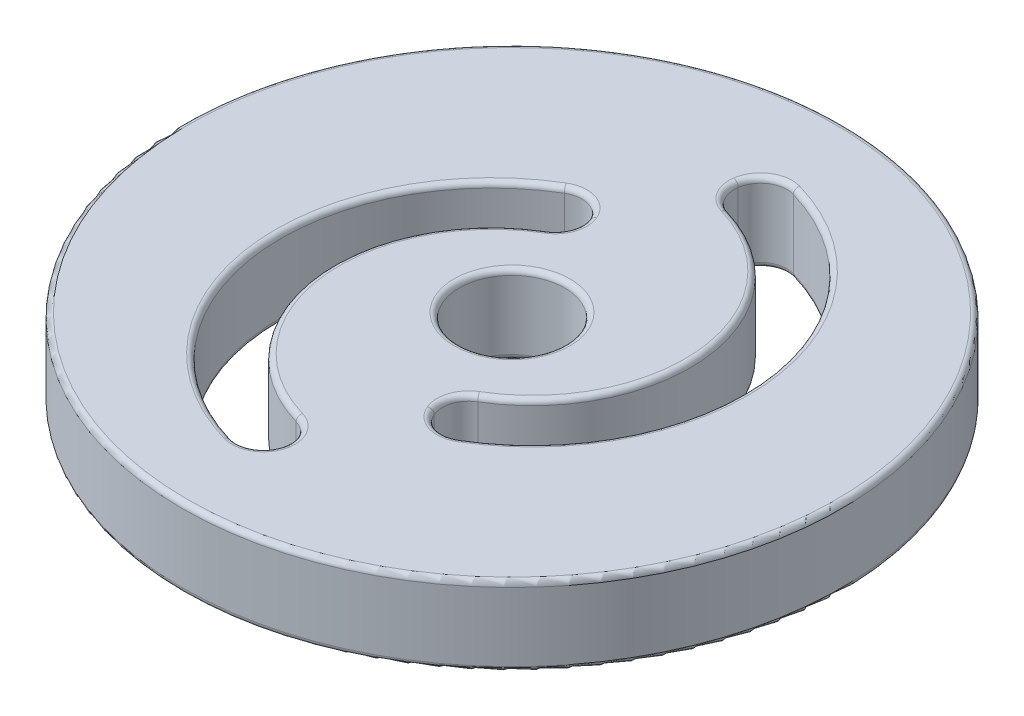
SolidWorks part; units mm, degrees
ref_plane "前视基准面" through (0, 0, 0) normal (0, 0, 1) x (1, 0, 0)
ref_plane "上视基准面" through (0, 0, 0) normal (0, 1, 0) x (1, 0, 0)
ref_plane "右视基准面" through (0, 0, 0) normal (1, 0, 0) x (0, 0, -1)
other "Configuration Table"
sketch "草图1" plane through (0, 0, 0) normal (0, 1, 0) x (1, 0, 0)
  circle A0 centre (0, 0) radius 125
  circle A1 centre (0, 0) radius 20
  dimension "D1" = 40
  dimension "D2" = 250
extrude "凸台-拉伸1" add sketch "草图1" along normal blind 30
sketch "草图2" plane through (0, 30, 0) normal (0, 1, 0) x (1, 0, 0)
  line L0 (0, 0) -> (0, 150) construction
  line L1 (0, 0) -> (-60.6659, 166.6783) construction
  line L2 (1.3957, 96.5021) -> (-1.3957, 76.6979)
  line L3 (13.256, -37.7534) -> (20.9461, -56.2159)
  line L6 (-13.256, 37.7534) -> (-20.9461, 56.2159)
  line L7 (-1.3957, -96.5021) -> (1.3957, -76.6979)
  arc A0 (0, 86.6) -> (17.101, -46.9846) centre (-9.7443, 17.4657) cw construction
  arc A1 (-1.3957, 76.6979) -> (13.256, -37.7534) centre (-9.7443, 17.4657) cw
  arc A2 (1.3957, 96.5021) -> (20.9461, -56.2159) centre (-9.7443, 17.4657) cw
  arc A3 (-1.3957, 76.6979) -> (13.256, -37.7534) centre (-9.7443, 17.4657) cw construction
  circle A4 centre (0, 0) radius 20 construction
  arc A5 (0, 86.6) -> (17.101, -46.9846) centre (-9.7443, 17.4657) cw construction
  arc A8 (-1.3957, -96.5021) -> (-20.9461, 56.2159) centre (9.7443, -17.4657) cw
  arc A9 (1.3957, -76.6979) -> (-13.256, 37.7534) centre (9.7443, -17.4657) cw
  arc A10 (0, -86.6) -> (-17.101, 46.9846) centre (9.7443, -17.4657) cw construction
  point P27 (0, 0)
  point P30 (1.3102, 1.6636)
  dimension "D1" = 20
  dimension "D2" = 86.6
  dimension "D3" = 50
  dimension "D4" = 10
  dimension "D5" = 10
  dimension "D6" = 2
extrude "切除-拉伸1" cut sketch "草图2" against normal blind 30
fillet "圆角3" radius 10 8 edges at (-20.9461, 15, -56.2159) (-13.256, 15, -37.7534) (-1.3957, 15, 96.5021) (1.3957, 15, 76.6979) (20.9461, 15, 56.2159) (13.256, 15, 37.7534) (-1.3957, 15, -76.6979) (1.3957, 15, -96.5021)
fillet "圆角4" radius 2 28 edges at (0, 0, 20) (0, 0, 125) (22.9206, 0, 51.971) (16.5595, 0, 39.3402) (49.5892, 0, -25.0613) (1.4016, 0, -79.0657) (4.3758, 0, -92.8915) (69.4273, 0, -27.6009) (-69.4273, 0, 27.6009) (-22.9206, 0, -51.971) (-16.5595, 0, -39.3402) (-49.5892, 0, 25.0613) (-1.4016, 0, 79.0657) (-4.3758, 0, 92.8915) (0, 30, 20) (0, 30, 125) (49.5892, 30, -25.0613) (16.5595, 30, 39.3402) (22.9206, 30, 51.971) (69.4273, 30, -27.6009) (4.3758, 30, -92.8915) (1.4016, 30, -79.0657) (-16.5595, 30, -39.3402) (-22.9206, 30, -51.971) (-69.4273, 30, 27.6009) (-4.3758, 30, 92.8915) (-1.4016, 30, 79.0657) (-49.5892, 30, 25.0613)
